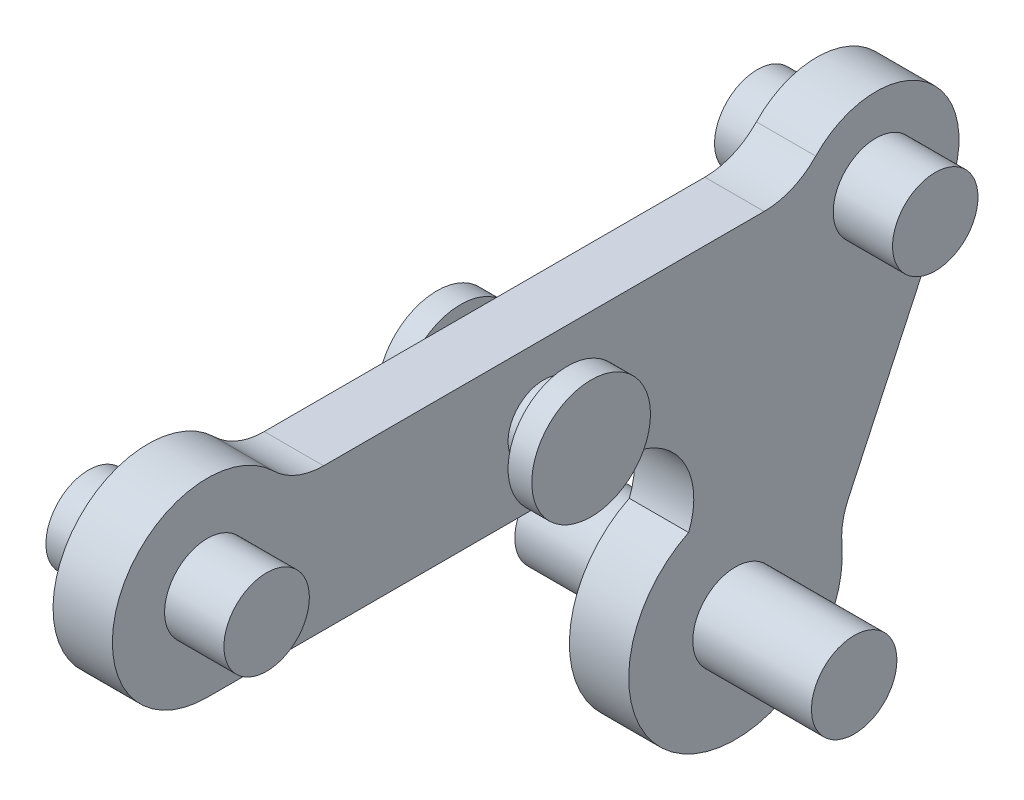
SolidWorks part; units mm, degrees
ref_plane "前视基准面" through (0, 0, 0) normal (0, 0, 1) x (1, 0, 0)
ref_plane "上视基准面" through (0, 0, 0) normal (0, 1, 0) x (1, 0, 0)
ref_plane "右视基准面" through (0, 0, 0) normal (1, 0, 0) x (0, 0, -1)
other "Configuration Table"
sketch "草图1" plane through (0, 0, 0) normal (1, 0, 0) x (0, 0, -1)
  line L1 (-28.1721, 1.4792) -> (-3.1721, 1.4792)
  line L2 (-28.1721, 1.4792) -> (-28.1721, -4.5208)
  line L3 (-28.1721, -4.5208) -> (-3.1721, -4.5208)
  line L4 (-3.1721, 1.4792) -> (-3.1721, -4.5208)
  line L5 (-3.1721, 1.4792) -> (3.1721, -1.4792)
  line L6 (-3.1721, 1.4792) -> (-9.0887, -11.2091)
  line L7 (-9.0887, -11.2091) -> (-2.7446, -14.1675)
  line L8 (3.1721, -1.4792) -> (-2.7446, -14.1675)
  circle A0 centre (-28.1721, -0.5208) radius 4
  circle A1 centre (0, 0) radius 3.5
  circle A2 centre (-5.9167, -12.6883) radius 4.5
  circle A3 centre (-28.1721, -0.5208) radius 2
  circle A4 centre (0, 0) radius 2
  circle A5 centre (-5.9167, -12.6883) radius 2
  dimension "D5" = 8
  dimension "D6" = 7
  dimension "D7" = 9
  dimension "D9" = 4
  dimension "D1" = 6
  dimension "D3" = 65
  dimension "D4" = 25
  dimension "D8" = 14
extrude "凸台-拉伸1" add sketch "草图1" along normal blind 1.25 contours A0 | L1 L4 L3 L2 | A1 | L5 L8 L7 L6 | A2
extrude "切除-拉伸1" cut sketch "草图1<3>" along normal through all contours A3 | A4 | A5
sketch "草图1<3>" plane through (0, 0, 0) normal (1, 0, 0) x (0, 0, -1) same geometry as "草图1"
fillet "圆角1" radius 3 5 edges at (0.625, -11.604, 1.5492) (0.625, -1.4792, -3.1721) (0.625, 1.4792, 3.1721) (0.625, 1.4792, 24.708) (0.625, -4.5208, 5.9699)
sketch "草图2" plane through (1.25, 0, 0) normal (1, 0, 0) x (0, 0, -1)
  circle A0 centre (0, 0) radius 2
  circle A1 centre (-5.9167, -12.6883) radius 2
  circle A2 centre (-28.1721, -0.5208) radius 2
  circle A3 centre (0, 0) radius 1.8
  circle A4 centre (-5.9167, -12.6883) radius 1.8
  circle A5 centre (-28.1721, -0.5208) radius 1.8
  dimension "D1" = 4
  dimension "D2" = 3.6
extrude "凸台-拉伸2" add sketch "草图2" against normal up to surface (1.25 mm away) contours A2 | A0 | A1 up to face at (0, -0.5208, 26.1721)
extrude "凸台-拉伸5" add sketch "草图2<5>" along normal blind 2.5 contours A5 | A3 region at (1.25, 0, 0) region at (1.25, -0.5208, 28.1721)
sketch "草图2<5>" plane through (1.25, 0, 0) normal (1, 0, 0) x (0, 0, -1) same geometry as "草图2"
extrude "凸台-拉伸7" add sketch "草图2<7>" along normal blind 5 contours A4 region at (1.25, -12.6883, 5.9167)
sketch "草图2<7>" plane through (1.25, 0, 0) normal (1, 0, 0) x (0, 0, -1) same geometry as "草图2"
sketch "草图3" plane through (1.25, 0, 0) normal (1, 0, 0) x (0, 0, -1)
  line L0 (-14, 1.4792) -> (-14, -4.5208) construction
  line L1 (-23.2731, 1.4792) -> (-4.7103, 1.4792) construction
  line L2 (-28.1721, -4.5208) -> (-10.6745, -4.5208) construction
  circle A0 centre (-14, -1.5208) radius 1.5
  circle A1 centre (-14, -1.5208) radius 2.5
  dimension "D1" = 3
  dimension "D3" = 5
  dimension "D2" = 14
extrude "凸台-拉伸8" add sketch "草图3" along normal blind 1 contours A0 L0 | L0 A0 region at (1.25, -1.5208, 13.3634) region at (1.25, -1.5208, 14.6366)
extrude "凸台-拉伸9" add sketch "草图3<3>" along normal blind 1 from surface contours A1 starting at face at (2.25, -1.5208, 12.5)
sketch "草图3<3>" plane through (1.25, 0, 0) normal (1, 0, 0) x (0, 0, -1) same geometry as "草图3"
ref_plane "基准面1" through (0, 0, 0) normal (-1, 0, 0) x (0, 0, 1)
mirror "镜向1" about plane through (0, 0, 0) normal (-1, 0, 0) of bodies 117 113
